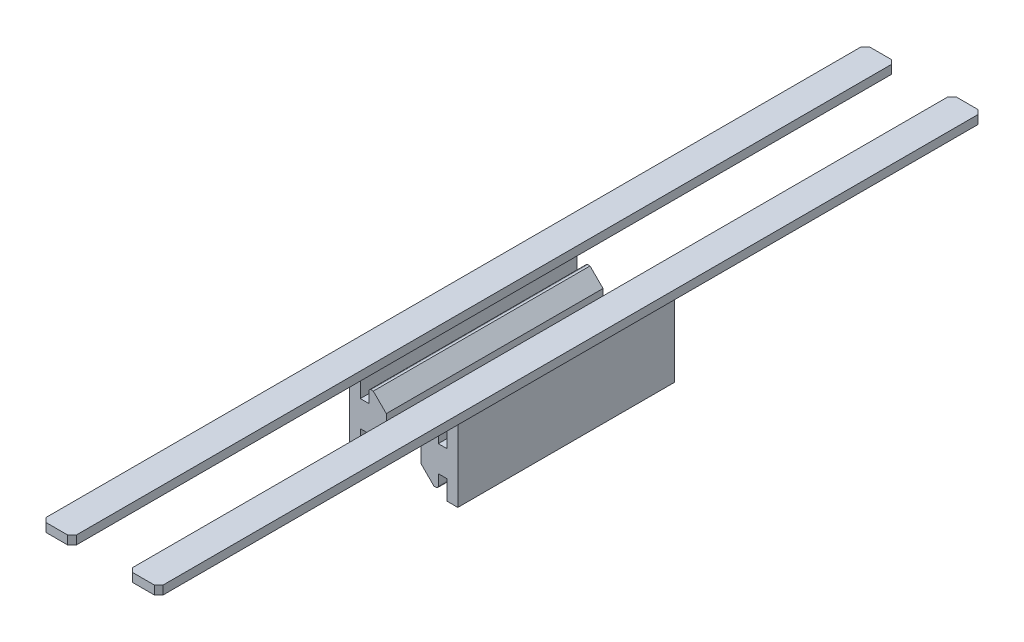
SolidWorks part; units mm, degrees
material "PLA"
ref_plane "Piano frontale" through (0, 0, 0) normal (0, 0, 1) x (1, 0, 0)
ref_plane "Piano superiore" through (0, 0, 0) normal (0, 1, 0) x (1, 0, 0)
ref_plane "Piano destro" through (0, 0, 0) normal (1, 0, 0) x (0, 0, -1)
sketch "Schizzo1" plane through (0, 0, 0) normal (0, 0, 1) x (1, 0, 0)
  line L15 (0, 0) -> (16.7322, 0) construction
  line L16 (0, -3) -> (0, 3)
  line L17 (0, 3) -> (3, 6)
  line L18 (6, 3) -> (6, -3)
  line L19 (6, 0) -> (0, 0)
  line L20 (3, 6) -> (4, 6)
  line L21 (4, 6) -> (4, 3)
  line L22 (4, 3) -> (6, 3)
  line L23 (4, -3) -> (6, -3)
  line L24 (4, -6) -> (4, -3)
  line L25 (3, -6) -> (4, -6)
  line L26 (0, -3) -> (3, -6)
  line L27 (0, 0) -> (-4, 0) construction
  line L28 (-4, 9.8277) -> (-4, -9.8277) construction
  line L29 (-12, 3) -> (-14, 3)
  line L30 (-12, 6) -> (-12, 3)
  line L31 (-11, 6) -> (-12, 6)
  line L32 (-8, 3) -> (-11, 6)
  line L33 (-8, -3) -> (-8, 3)
  line L34 (-8, -3) -> (-11, -6)
  line L35 (-11, -6) -> (-12, -6)
  line L36 (-12, -6) -> (-12, -3)
  line L37 (-12, -3) -> (-14, -3)
  line L38 (-14, 3) -> (-14, -3)
  point P18 (-4, 0)
  dimension "D1" = 3
  dimension "D2" = 6
  dimension "D3" = 45
  dimension "D4" = 1
  dimension "D5" = 3
  dimension "D6" = 2
  dimension "D7" = 4
extrude "Estrusione-Estrusione1" add sketch "Schizzo1" along normal blind 70 contours L22 L21 L20 L17 L16 L19 L18 | L16 L26 L25 L24 L23 L18 L19 region at (2.8824, -2.2941, 0) region at (2.8824, 2.2941, 0)
sketch "Schizzo2" plane through (0, 0, 70) normal (0, 0, 1) x (1, 0, 0)
  line L0 (6, 3) -> (6, 12)
  line L1 (6, 12) -> (8.5, 12)
  line L2 (8.5, 12) -> (8.5, -7.5)
  line L3 (8.5, -7.5) -> (6, -7.5)
  line L4 (6, -7.5) -> (6, -3)
  line L15 (6, 3) -> (4, 3)
  line L16 (4, 3) -> (4, 6)
  line L17 (4, 6) -> (3, 6)
  line L18 (3, 6) -> (0, 3)
  line L19 (0, 3) -> (0, -3)
  line L20 (0, -3) -> (3, -6)
  line L21 (3, -6) -> (4, -6)
  line L22 (4, -6) -> (4, -3)
  line L23 (4, -3) -> (6, -3)
  line L24 (6, -3) -> (6, 3)
  line L25 (6, 3) -> (4, 3)
  line L26 (4, 3) -> (4, 6)
  line L27 (4, 6) -> (3, 6)
  line L28 (3, 6) -> (0, 3)
  line L29 (0, 3) -> (0, -3)
  line L30 (0, -3) -> (3, -6)
  line L31 (3, -6) -> (4, -6)
  line L32 (4, -6) -> (4, -3)
  line L33 (4, -3) -> (6, -3)
  dimension "D1" = 9
  dimension "D2" = 2.5
  dimension "D3" = 4.5
  dimension "D4" = 0
extrude "Estrusione-Estrusione2" add sketch "Schizzo2" against normal blind 70
extrude "Estrusione-Estrusione3" add sketch "Schizzo1<3>" along normal blind 70 separate body contours L29 L38 L37 L36 L35 L34 L33 L32 L31 L30 region at (-10.8824, 0, 0)
sketch "Schizzo1<3>" plane through (0, 0, 0) normal (0, 0, 1) x (1, 0, 0) same geometry as "Schizzo1"
sketch "Schizzo3" plane through (0, 0, 70) normal (0, 0, 1) x (1, 0, 0)
  line L0 (-14, -3) -> (-14, -7.5)
  line L1 (-14, -7.5) -> (-16.5, -7.5)
  line L2 (-12, -3) -> (-14, -3) construction
  line L3 (-16.5, 12) -> (-14, 12)
  line L4 (-14, 12) -> (-14, 3)
  line L5 (-16.5, 12) -> (-16.5, -7.5)
  line L16 (-12, 3) -> (-14, 3)
  line L17 (-14, 3) -> (-14, -3)
  line L18 (-14, -3) -> (-12, -3)
  line L19 (-12, -3) -> (-12, -6)
  line L20 (-12, -6) -> (-11, -6)
  line L21 (-11, -6) -> (-8, -3)
  line L22 (-8, -3) -> (-8, 3)
  line L23 (-8, 3) -> (-11, 6)
  line L24 (-11, 6) -> (-12, 6)
  line L25 (-12, 6) -> (-12, 3)
  line L26 (-12, 3) -> (-14, 3)
  line L28 (-14, -3) -> (-12, -3)
  line L29 (-12, -3) -> (-12, -6)
  line L30 (-12, -6) -> (-11, -6)
  line L31 (-11, -6) -> (-8, -3)
  line L32 (-8, -3) -> (-8, 3)
  line L33 (-8, 3) -> (-11, 6)
  line L34 (-11, 6) -> (-12, 6)
  line L35 (-12, 6) -> (-12, 3)
  dimension "D1" = 2.5
  dimension "D2" = 9
  dimension "D3" = 4.5
  dimension "D4" = 0
extrude "Estrusione-Estrusione4" add sketch "Schizzo3" against normal blind 70
sketch "Schizzo4" plane through (0, 0, 70) normal (0, 0, 1) x (1, 0, 0)
  line L0 (-16.5, 12) -> (-16.5, 10)
  line L1 (-16.5, 12) -> (-16.5, -7.5) construction
  line L2 (-16.5, 10) -> (8.5, 10)
  line L3 (8.5, 10) -> (8.5, 12)
  line L4 (8.5, 12) -> (-16.5, 12)
  line L5 (8.5, -7.5) -> (8.5, 12) construction
  dimension "D1" = 2
extrude "Estrusione-Estrusione5" add sketch "Schizzo4" against normal blind 70
sketch "Schizzo6" plane through (0, 12, 0) normal (0, 1, 0) x (1, 0, 0)
  line L0 (8.5, 0) -> (-16.5, 0) construction
  line L1 (-10.5, 0) -> (2.5, 0)
  line L2 (-10.5, 0) -> (-10.5, -70)
  line L3 (-10.5, -70) -> (2.5, -70)
  line L4 (2.5, 0) -> (2.5, -70)
  line L5 (8.5, -70) -> (-16.5, -70) construction
  line L6 (-17.5, 0) -> (-10.5, 0)
  line L7 (2.5, 0) -> (9.5, 0)
  line L8 (2.5, -70) -> (9.5, -70)
  line L9 (9.5, -70) -> (9.5, 0)
  line L10 (-17.5, -70) -> (-10.5, -70)
  line L12 (-17.5, -70) -> (-17.5, 0)
  point P8 (-4, -70)
  point P10 (-4, -70)
  point P17 (2.5, -70)
  line M10 (8.5, 0) -> (-16.5, 0)
  line M11 (-16.5, 0) -> (-16.5, -70)
  line M12 (-16.5, -70) -> (8.5, -70)
  line M13 (8.5, -70) -> (8.5, 0)
  dimension "D1" = 7
  dimension "D2" = 7
  dimension "D3" = 13
extrude "Estrusione-Estrusione6" add sketch "Schizzo6" against normal blind 2 contours L2 M10 M11 M12 | L4 M10 M12 M13 | L8 L9 L7 M13 | L12 L10 L6 M11 region at (-13.5, 12, 35) region at (5.5, 12, 35) region at (-17, 12, 35) region at (9, 12, 35)
extrude "Taglio-Estrusione1" cut sketch "Schizzo6<3>" against normal blind 2 contours L4 L2 M10 M12 region at (-4, 12, 35)
sketch "Schizzo6<3>" plane through (0, 12, 0) normal (0, 1, 0) x (1, 0, 0) same geometry as "Schizzo6"
fillet "Raccordo1" radius 0.5 2 edges at (4, 6, 35) (4, -6, 35)
fillet "Raccordo2" radius 0.5 2 edges at (-12, -6, 35) (-12, 6, 35)
sketch "Schizzo7" plane through (0, 0, 70) normal (0, 0, 1) x (1, 0, 0)
  line L1 (-17.5, 12) -> (-10.5, 12)
  line L2 (-17.5, 12) -> (-17.5, 10)
  line L3 (-17.5, 10) -> (-10.5, 10)
  line L4 (-10.5, 12) -> (-10.5, 10)
  line L5 (9.5, 12) -> (2.5, 12)
  line L6 (9.5, 12) -> (9.5, 10)
  line L7 (9.5, 10) -> (2.5, 10)
  line L8 (2.5, 12) -> (2.5, 10)
extrude "Estrusione-Estrusione8" add sketch "Schizzo7" along normal blind 60
sketch "Schizzo8" plane through (0, 0, 0) normal (0, 0, -1) x (-1, 0, 0)
  line L1 (-9.5, 12) -> (-2.5, 12)
  line L2 (-9.5, 12) -> (-9.5, 10)
  line L3 (-9.5, 10) -> (-2.5, 10)
  line L4 (-2.5, 12) -> (-2.5, 10)
  line L5 (10.5, 12) -> (17.5, 12)
  line L6 (10.5, 12) -> (10.5, 10)
  line L7 (10.5, 10) -> (17.5, 10)
  line L8 (17.5, 12) -> (17.5, 10)
extrude "Estrusione-Estrusione9" add sketch "Schizzo8" along normal blind 60
sketch "Schizzo9" plane through (8.5, 0, 0) normal (1, 0, 0) x (0, 0, -1)
  line L0 (0, 10) -> (-70, 10) construction
  line L1 (-70, -7.5) -> (-60, -7.5)
  line L2 (-70, -7.5) -> (-70, 10)
  line L3 (-70, 10) -> (-60, 10)
  line L4 (-60, -7.5) -> (-60, 10)
  line L6 (0, -7.5) -> (-10, -7.5)
  line L7 (0, -7.5) -> (0, 10)
  line L8 (0, 10) -> (-10, 10)
  line L9 (-10, -7.5) -> (-10, 10)
  dimension "D1" = 10
  dimension "D2" = 10
extrude "Taglio-Estrusione2" cut sketch "Schizzo9" against normal blind 60
chamfer "Smusso1" distance 1 angle 45 4 edges at (-17.5, 11, -60) (-10.5, 11, -60) (-10.5, 11, 130) (-17.5, 11, 130)
chamfer "Smusso2" distance 1 angle 45 4 edges at (2.5, 11, 130) (9.5, 11, 130) (9.5, 11, -60) (2.5, 11, -60)
sketch "Schizzo10" plane through (0, 12, 0) normal (0, 1, 0) x (1, 0, 0)
  line L0 (2.5, 59) -> (2.5, -129) construction
  line L1 (8.5, 60) -> (3.5, 60)
  line L2 (9.5, 59) -> (9.5, -10)
  line L3 (9.5, -10) -> (2.5, -10)
  line L4 (2.5, 59) -> (2.5, -10)
  line L6 (3.5, 60) -> (8.5, 60) construction
  line L7 (9.5, 59) -> (8.5, 60)
  line L8 (3.5, 60) -> (2.5, 59)
  line L9 (9.5, -129) -> (9.5, 59) construction
  line L10 (8.5, -130) -> (3.5, -130)
  line L11 (9.5, -129) -> (9.5, -60)
  line L12 (9.5, -60) -> (2.5, -60)
  line L13 (2.5, -129) -> (2.5, -60)
  line L14 (8.5, -130) -> (3.5, -130) construction
  line L15 (9.5, -129) -> (8.5, -130)
  line L16 (3.5, -130) -> (2.5, -129)
  point P0 (9.5, 60)
  point P3 (2.5, 60)
  point P14 (9.5, -130)
  point P17 (2.5, -130)
  dimension "D1" = 7
  dimension "D2" = 70
  dimension "D3" = 7
  dimension "D4" = 70
